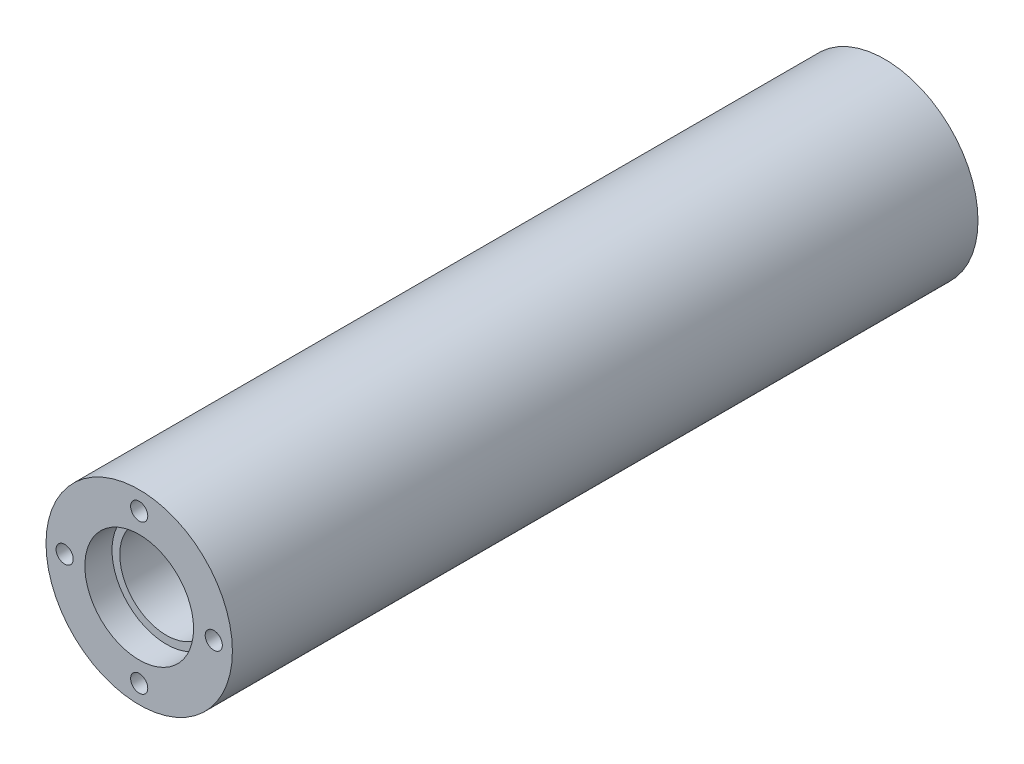
SolidWorks part; units mm, degrees
other "Markup1"
sketch "Sketch4" plane through (19.05, 19.05, 152.4) normal (0.8805, 0.4318, 0.1958) x (0.1841, 0.0692, -0.9805)
ref_plane "Front Plane" through (0, 0, 0) normal (0, 0, 1) x (1, 0, 0)
ref_plane "Top Plane" through (0, 0, 0) normal (0, 1, 0) x (1, 0, 0)
ref_plane "Right Plane" through (0, 0, 0) normal (1, 0, 0) x (0, 0, -1)
sketch "Sketch1" plane through (0, 0, 0) normal (0, 0, 1) x (1, 0, 0)
  circle A0 centre (0, 0) radius 19.05
  circle A1 centre (0, 0) radius 9.525
  dimension "D1" = 38.1
  dimension "D2" = 19.05
extrude "Boss-Extrude1" add sketch "Sketch1" along normal blind 152.4
sketch "Sketch2" plane through (0, 0, 0) normal (0, 0, -1) x (-1, 0, 0)
  circle A0 centre (0, 15.24) radius 1.7526
  circle A1 centre (15.24, 0) radius 1.7526
  circle A2 centre (0, -15.24) radius 1.7526
  circle A3 centre (-15.24, 0) radius 1.7526
  point P12 (0, 0)
  dimension "D1" = 3.5052
  dimension "D2" = 15.24
  dimension "D3" = 4
extrude "Cut-Extrude1" cut sketch "Sketch2" against normal blind 9.525
sketch "Sketch3" plane through (0, 0, 152.4) normal (0, 0, 1) x (1, 0, 0)
  circle A0 centre (0, 15.24) radius 1.7526
  circle A1 centre (15.24, 0) radius 1.7526
  circle A2 centre (0, -15.24) radius 1.7526
  circle A3 centre (-15.24, 0) radius 1.7526
  point P2 (0, 0)
  point P9 (0, 0)
  point P12 (0, 0)
  point P15 (0, 0)
  point P16 (0, 0)
  dimension "D2" = 3.5052
  dimension "D1" = 15.24
  dimension "D3" = 4
extrude "Cut-Extrude2" cut sketch "Sketch3" against normal blind 9.525
sketch "Sketch6" plane through (0, 0, 152.4) normal (0, 0, 1) x (1, 0, 0)
  circle A0 centre (0, 0) radius 11.1125
  dimension "D1" = 22.225
extrude "Cut-Extrude3" cut sketch "Sketch6" against normal blind 5.5562
sketch "Sketch7" plane through (0, 0, 0) normal (0, 0, -1) x (-1, 0, 0)
  circle A0 centre (0, 0) radius 11.1125
  dimension "D1" = 22.225
extrude "Cut-Extrude4" cut sketch "Sketch7" against normal blind 5.5562
